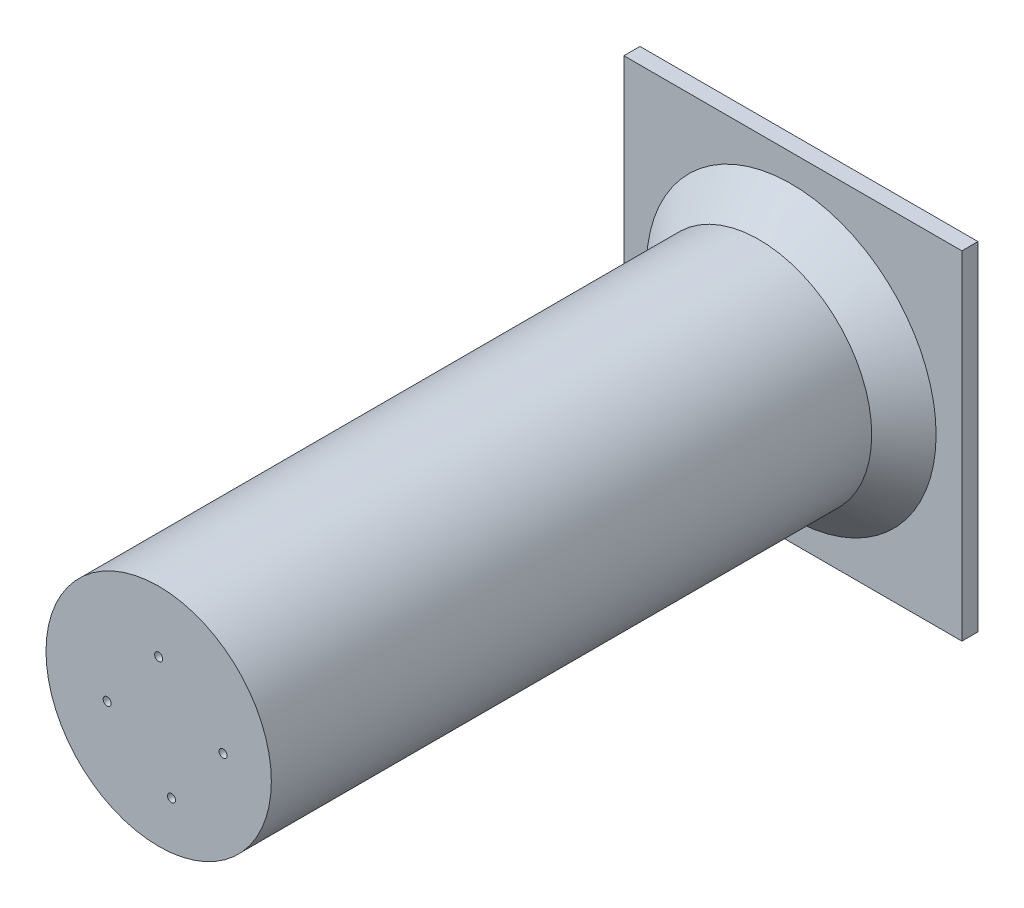
SolidWorks part; units mm, degrees
ref_plane "Alzado" through (0, 0, 0) normal (0, 0, 1) x (1, 0, 0)
ref_plane "Planta" through (0, 0, 0) normal (0, 1, 0) x (1, 0, 0)
ref_plane "Vista lateral" through (0, 0, 0) normal (1, 0, 0) x (0, 0, -1)
sketch "Croquis1" plane through (0, 0, 0) normal (0, 0, 1) x (1, 0, 0)
  line L1 (-117.2917, 97.7627) -> (131.4683, 97.7627)
  line L2 (-117.2917, 97.7627) -> (-117.2917, -97.2373)
  line L3 (-117.2917, -97.2373) -> (131.4683, -97.2373)
  line L4 (131.4683, 97.7627) -> (131.4683, -97.2373)
  dimension "D1" = 248.76
  dimension "D2" = 195
extrude "Saliente-Extruir1" add sketch "Croquis1" along normal blind 5
sketch "Croquis2" plane through (0, 0, 5) normal (0, 0, 1) x (1, 0, 0)
  line L0 (-117.2917, 0.2627) -> (131.4683, 0.2627) construction
  line L1 (-117.2917, 97.7627) -> (-117.2917, -97.2373) construction
  line L2 (131.4683, -97.2373) -> (131.4683, 97.7627) construction
  line L3 (-117.2917, -97.2373) -> (-69.2917, -97.2373)
  line L4 (-117.2917, -97.2373) -> (131.4683, -97.2373) construction
  line L5 (-69.2917, -97.2373) -> (-69.2917, -67.2373)
  line L6 (-69.2917, -67.2373) -> (-117.2917, -67.2373)
  line L7 (-117.2917, -67.2373) -> (-117.2917, -97.2373)
  line L8 (131.4683, 67.7627) -> (101.4683, 67.7627)
  line L9 (131.4683, -97.2373) -> (101.4683, -97.2373)
  line L10 (131.4683, -97.2373) -> (131.4683, -67.2373)
  line L11 (131.4683, -67.2373) -> (101.4683, -67.2373)
  line L12 (101.4683, -97.2373) -> (101.4683, -67.2373)
  line L13 (101.4683, 97.7627) -> (101.4683, 67.7627)
  line L14 (131.4683, 97.7627) -> (101.4683, 97.7627)
  line L15 (131.4683, 97.7627) -> (131.4683, 67.7627)
  line L16 (-69.2917, 67.7627) -> (-117.2917, 67.7627)
  line L17 (-69.2917, 97.7627) -> (-69.2917, 67.7627)
  line L18 (-117.2917, 97.7627) -> (-69.2917, 97.7627)
  line L19 (-117.2917, 67.7627) -> (-117.2917, 97.7627)
  dimension "D1" = 48
  dimension "D2" = 30
  dimension "D3" = 30
  dimension "D4" = 30
extrude "Cortar-Extruir1" cut sketch "Croquis2" against normal blind 2
sketch "Croquis3" plane through (0, 0, 5) normal (0, 0, 1) x (1, 0, 0)
  line L0 (-69.2917, 97.7627) -> (-117.2917, 97.7627) construction
  line L1 (116.4683, 83.7627) -> (116.4683, 67.7627) construction
  line L3 (116.4683, -83.2373) -> (116.4683, -67.2373) construction
  line L5 (131.4683, -67.2373) -> (101.4683, -67.2373) construction
  line L6 (101.4683, 67.7627) -> (131.4683, 67.7627) construction
  line L7 (-93.2917, 83.7627) -> (-93.2917, 67.7627) construction
  line L8 (-117.2917, 67.7627) -> (-69.2917, 67.7627) construction
  line L9 (-93.2917, -83.2373) -> (-93.2917, -67.2373) construction
  line L10 (-69.2917, -67.2373) -> (-117.2917, -67.2373) construction
  circle A0 centre (-93.2917, 83.7627) radius 2.375
  circle A1 centre (-93.2917, -83.2373) radius 2.375
  circle A2 centre (116.4683, 83.7627) radius 2.375
  circle A3 centre (116.4683, -83.2373) radius 2.375
  dimension "D2" = 4.75
  dimension "D3" = 4.75
  dimension "D5" = 4.75
  dimension "D6" = 4.75
  dimension "D1" = 14
  dimension "D4" = 14
  dimension "D7" = 209.76
  dimension "D8" = 16
  dimension "D9" = 16
extrude "Cortar-Extruir2" cut sketch "Croquis3" against normal blind 10
sketch "Croquis4" plane through (0, 0, 0) normal (0, 0, -1) x (-1, 0, 0)
  line L7 (-131.4683, 97.7627) -> (117.2917, 97.7627) construction
  line L9 (117.2917, 97.7627) -> (117.2917, -97.2373) construction
  circle A0 centre (55.1017, 0.2627) radius 35
  dimension "D3" = 70
  dimension "D1" = 62.19
  dimension "D2" = 97.5
extrude "Saliente-Extruir2" add sketch "Croquis4" along normal blind 196.5 contours A0
sketch "Croquis5" plane through (0, 0, 0) normal (0, 0, -1) x (-1, 0, 0)
  line L0 (-131.4683, 0.2627) -> (117.2917, 0.2627) construction
  line L1 (-131.4683, -97.2373) -> (-131.4683, 97.7627) construction
  line L2 (117.2917, 97.7627) -> (117.2917, -97.2373) construction
  circle A0 centre (-76.9683, 0.2627) radius 12.5
  dimension "D1" = 25
  dimension "D2" = 54.5
extrude "Cortar-Extruir3" cut sketch "Croquis5" against normal blind 10
sketch "Croquis6" plane through (0, 0, 0) normal (0, 0, -1) x (-1, 0, 0)
  line L0 (-131.4683, 97.7627) -> (117.2917, 97.7627) construction
  line L1 (-7.0883, 97.7627) -> (-7.0883, -97.2373)
  line L2 (117.2917, -97.2373) -> (-131.4683, -97.2373) construction
  line L3 (-7.0883, 97.7627) -> (117.2917, 97.7627)
  line L4 (117.2917, 97.7627) -> (117.2917, -97.2373)
  line L5 (117.2917, -97.2373) -> (-7.0883, -97.2373)
  line L6 (-131.4683, 0.2627) -> (56.0317, 0.2627)
  line L7 (-131.4683, -97.2373) -> (-131.4683, 97.7627) construction
  circle A1 centre (56.0317, 0.2627) radius 100
  dimension "D1" = 200
  dimension "D2" = 187.5
sketch "Croquis9" plane through (0, 97.7627, 0) normal (0, 1, 0) x (1, 0, 0)
  line L0 (7.0883, 0) -> (7.0883, -5)
  line L1 (131.4683, 0) -> (-117.2917, 0) construction
  line L2 (101.4683, -5) -> (-69.2917, -5) construction
ref_plane "Plano3" through (7.0883, 0, 0) normal (1, 0, 0) x (0, 0, -1)
sketch "Croquis12" plane through (7.0883, 0, 0) normal (1, 0, 0) x (0, 0, -1)
  line L0 (0, 97.7627) -> (0, 67.7627)
  line L1 (0, 67.7627) -> (12, 67.7627)
  line L2 (12, 67.7627) -> (12, 97.7627)
  line L3 (12, 97.7627) -> (0, 97.7627)
  line L4 (0, -97.2373) -> (12, -97.2373)
  line L5 (12, -97.2373) -> (12, -67.2373)
  line L6 (12, -67.2373) -> (0, -67.2373)
  line L7 (0, -67.2373) -> (0, -97.2373)
  dimension "D1" = 30
  dimension "D2" = 12
  dimension "D3" = 30
  dimension "D4" = 12
extrude "Saliente-Extruir3" add sketch "Croquis12" along normal mid plane 8
fillet "Redondeo1" radius 10 2 edges at (7.0883, -67.2373, 0) (7.0883, 67.7627, 0)
fillet "Redondeo2" radius 10 2 edges at (7.0883, 67.7627, -12) (7.0883, -67.2373, -12)
fillet "Redondeo3" radius 10 2 edges at (7.0883, -97.2373, -12) (7.0883, 97.7627, -12)
sketch "Croquis13" plane through (11.0883, 0, 0) normal (1, 0, 0) x (0, 0, -1)
  line L0 (-5, 0.2627) -> (196.5, 0.2627) construction
  line L1 (-5, -67.2373) -> (-5, 67.7627) construction
  line L2 (196.5, -34.7373) -> (196.5, 35.2627) construction
  line L3 (6, 87.7627) -> (12, 87.7627) construction
  line L4 (6, 87.7627) -> (6, 77.7627) construction
  circle A0 centre (6, 87.7627) radius 1.625
  circle A1 centre (6, 77.7627) radius 1.625
  circle A2 centre (6, -77.2373) radius 1.625
  circle A3 centre (6, -87.2373) radius 1.625
  dimension "D3" = 3.25
  dimension "D4" = 3.25
  dimension "D1" = 6
extrude "Cortar-Extruir5" cut sketch "Croquis13" against normal through all both and the other way through all
sketch "Croquis14" plane through (0, 0, 0) normal (0, 0, -1) x (-1, 0, 0)
  line L0 (-7.0883, 97.7627) -> (-7.0883, -97.2373)
  line L1 (-7.0883, 97.7627) -> (117.2917, 97.7627)
  line L2 (117.2917, 97.7627) -> (117.2917, -97.2373)
  line L3 (117.2917, -97.2373) -> (-7.0883, -97.2373)
sketch "Croquis15" plane through (0, 0, 5) normal (0, 0, 1) x (1, 0, 0)
  line L0 (111.4683, 67.7627) -> (131.4683, 67.7627)
  line L1 (111.4683, 67.7627) -> (111.4683, 60.0127)
  line L2 (131.4683, -67.2373) -> (101.4683, -67.2373) construction
  line L3 (111.4683, -67.2373) -> (111.4683, -59.4873)
  line L4 (111.4683, -59.4873) -> (125.2183, -59.4873)
  line L5 (125.2183, -59.4873) -> (125.2183, 60.0127)
  line L6 (111.4683, 60.0127) -> (125.2183, 60.0127)
  line L7 (111.4683, -67.2373) -> (131.4683, -67.2373)
  line L10 (131.4683, -67.2373) -> (131.4683, 67.7627)
  dimension "D1" = 119.5
  dimension "D2" = 7.75
  dimension "D3" = 13.75
extrude "Cortar-Extruir7" cut sketch "Croquis15" against normal blind 2
sketch "Croquis16" plane through (0, 0, 5) normal (0, 0, 1) x (1, 0, 0)
  circle A1 centre (-55.1017, 16.2627) radius 1.25
  circle A2 centre (-35.1017, 0.2627) radius 1.25
  circle A3 centre (-51.1017, -19.7373) radius 1.25
  circle A4 centre (-71.1017, -3.7373) radius 1.25
  dimension "D1" = 16
  dimension "D3" = 2.5
  dimension "D4" = 4
extrude "Cortar-Extruir9" cut sketch "Croquis16" against normal blind 20
sketch "Croquis20" plane through (0, -97.2373, 0) normal (0, -1, 0) x (1, 0, 0)
  line L0 (-117.2917, 10.5315) -> (-117.2917, 0)
  line L1 (-117.2917, 0) -> (3.0883, 0)
  line L2 (3.0883, 0) -> (3.0883, -12)
  line L3 (3.0883, -12) -> (11.0883, -12)
  line L4 (11.0883, -12) -> (11.0883, 0)
  line L5 (11.0883, 0) -> (131.4683, 0)
  line L6 (131.4683, 0) -> (131.4683, 10.5315)
  line L7 (131.4683, 10.5315) -> (-117.2917, 10.5315)
extrude "Cortar-Extruir17" cut sketch "Croquis20" against normal through all both and the other way through all
sketch "Croquis21" plane through (0, 0, -196.5) normal (0, 0, -1) x (-1, 0, 0)
  line L1 (2.0835, -51.2668) -> (107.0835, -51.2668)
  line L2 (2.0835, -51.2668) -> (2.0835, 53.7332)
  line L3 (2.0835, 53.7332) -> (107.0835, 53.7332)
  line L4 (107.0835, -51.2668) -> (107.0835, 53.7332)
  line L5 (2.0835, -51.2668) -> (107.0835, 53.7332) construction
  line L6 (2.0835, 53.7332) -> (107.0835, -51.2668) construction
  point P0 (54.5835, 1.2332)
  dimension "D1" = 105
  dimension "D2" = 105
extrude "Saliente-Extruir4" add sketch "Croquis21" along normal blind 5
chamfer "Chaflán1" distance 10 angle 45 1 edges at (-90.1017, 0.2627, -196.5)
